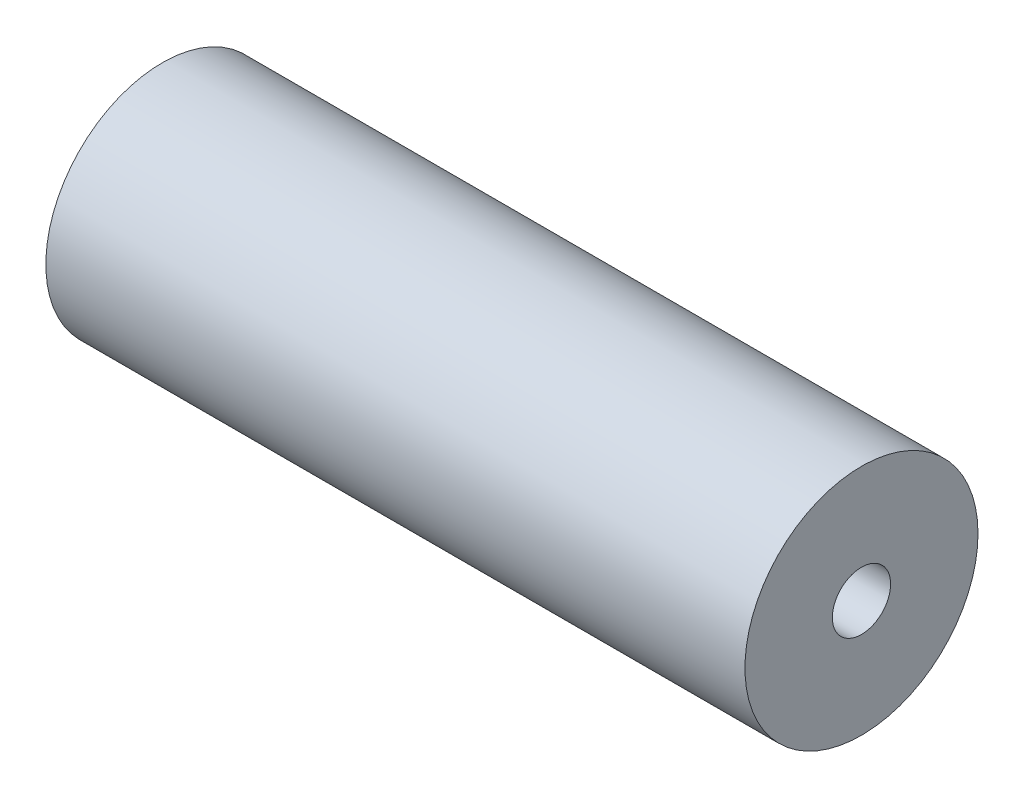
SolidWorks part; units mm, degrees
ref_plane "Plan de face" through (0, 0, 0) normal (0, 0, 1) x (1, 0, 0)
ref_plane "Plan de dessus" through (0, 0, 0) normal (0, 1, 0) x (1, 0, 0)
ref_plane "Plan de droite" through (0, 0, 0) normal (1, 0, 0) x (0, 0, -1)
sketch "Esquisse1" plane through (0, 0, 0) normal (1, 0, 0) x (0, 0, -1)
  circle A0 centre (0, 0) radius 10
extrude "Boss.-Extru.1" add sketch "Esquisse1" along normal blind 60
sketch "Esquisse2" plane through (0, 0, 0) normal (-1, 0, 0) x (0, 0, 1)
  circle A0 centre (0, 0) radius 2.5
extrude "Enlèv. mat.-Extru.1" cut sketch "Esquisse2" against normal blind 60
